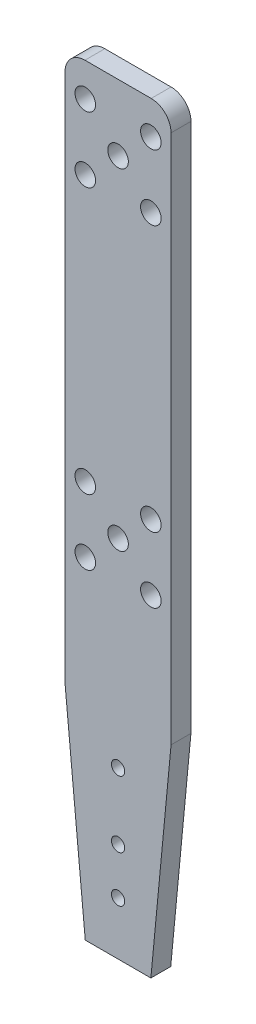
SolidWorks part; units mm, degrees
ref_plane "前视基准面" through (0, 0, 0) normal (0, 0, 1) x (1, 0, 0)
ref_plane "上视基准面" through (0, 0, 0) normal (0, 1, 0) x (1, 0, 0)
ref_plane "右视基准面" through (0, 0, 0) normal (1, 0, 0) x (0, 0, -1)
other "Configuration Table"
sketch "草图1" plane through (0, 0, 0) normal (0, 0, 1) x (1, 0, 0)
  line L0 (0, 60.2122) -> (0, -102.648) construction
  line L1 (-60.5647, 6.2167) -> (61.8958, 6.2167) construction
  line L2 (5, 16.2167) -> (-5, 16.2167)
  line L3 (-8, -66.7833) -> (-4, -108.7833)
  line L4 (0, -24.3301) -> (0, -46.8317) construction
  line L5 (8, -66.7833) -> (4, -108.7833)
  line L6 (-8, 13.2167) -> (-8, -66.7833)
  line L7 (-4, -108.7833) -> (4, -108.7833)
  line L8 (8, 13.2167) -> (8, -66.7833)
  line L12 (-27.2464, -43.7833) -> (27.2464, -43.7833) construction
  circle A0 centre (0, 6.2167) radius 7 construction
  circle A1 centre (-4.9497, 11.1665) radius 1.55
  circle A2 centre (4.9497, 11.1665) radius 1.55
  circle A3 centre (4.9497, 1.267) radius 1.55
  circle A4 centre (-4.9497, 1.267) radius 1.55
  circle A5 centre (0, -43.7833) radius 1.55
  circle A6 centre (0, -43.7833) radius 7 construction
  circle A7 centre (4.9497, -38.8335) radius 1.55
  circle A8 centre (-4.9497, -38.8335) radius 1.55
  arc A9 (8, 13.2167) -> (5, 16.2167) centre (5, 13.2167) ccw
  arc A10 (-8, 13.2167) -> (-5, 16.2167) centre (-5, 13.2167) cw
  circle A11 centre (4.9497, -48.733) radius 1.55
  circle A12 centre (-4.9497, -48.733) radius 1.55
  circle A13 centre (0, 6.2167) radius 1.55
  point P18 (0, 0)
  point P39 (0, -108.7833)
  point P44 (0, 6.2167)
  point P46 (0, -43.7833)
  dimension "D2" = 14
  dimension "D3" = 3.1
  dimension "D6" = 3.1
  dimension "D7" = 0
  dimension "D14" = 4
  dimension "D15" = 8
  dimension "D16" = 3.1
  dimension "D17" = 80
  dimension "D9" = 3
  dimension "D8" = 3.1
  dimension "D13" = 14
  dimension "D5" = 50
  dimension "D10" = 16
  dimension "D11" = 125
  dimension "D12" = 115
  dimension "D4" = 4
extrude "凸台-拉伸1" add sketch "草图1" along normal blind 3
sketch "草图2" plane through (0, 0, 0) normal (0, 0, -1) x (-1, 0, 0)
  line L0 (-14.1091, -98.7833) -> (16.5699, -98.7833)
  line L1 (16.5699, -98.7833) -> (16.5699, -119.0749)
  line L2 (16.5699, -119.0749) -> (-14.1091, -119.0749)
  line L3 (-14.1091, -119.0749) -> (-14.1091, -98.7833)
  line L4 (4, -108.7833) -> (-4, -108.7833) construction
  dimension "D1" = 10
extrude "切除-拉伸1" cut sketch "草图2" against normal blind 10
sketch "草图3" plane through (0, 0, 0) normal (0, 0, -1) x (-1, 0, 0)
  line L0 (4.9524, -98.7833) -> (-4.9524, -98.7833) construction
  circle A0 centre (0, -83.7833) radius 1
  circle A1 centre (0, -90.7833) radius 1
  circle A2 centre (0, -73.7833) radius 1
  dimension "D3" = 2
  dimension "D1" = 15
  dimension "D2" = 8
  dimension "D4" = 25
extrude "切除-拉伸2" cut sketch "草图3" against normal blind 20
